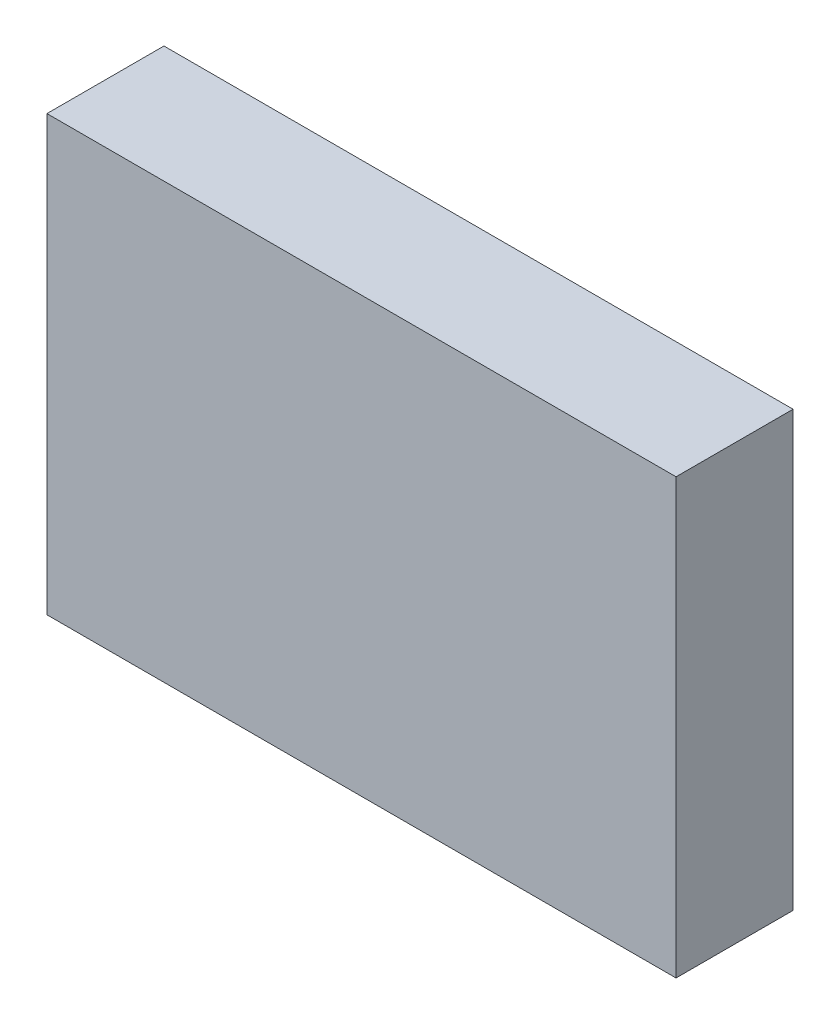
SolidWorks part; units mm, degrees
material "K110"
ref_plane "Front Plane" through (0, 0, 0) normal (0, 0, 1) x (1, 0, 0)
ref_plane "Top Plane" through (0, 0, 0) normal (0, 1, 0) x (1, 0, 0)
ref_plane "Right Plane" through (0, 0, 0) normal (1, 0, 0) x (0, 0, -1)
sketch "Sketch1" plane through (0, 0, 0) normal (0, 1, 0) x (1, 0, 0)
  line L1 (-40, -7.44) -> (40, -7.44)
  line L2 (-40, -7.44) -> (-40, 7.44)
  line L3 (-40, 7.44) -> (40, 7.44)
  line L4 (40, -7.44) -> (40, 7.44)
  line L5 (-40, -7.44) -> (40, 7.44) construction
  line L6 (-40, 7.44) -> (40, -7.44) construction
  point P0 (0, 0)
  dimension "D1" = 80
  dimension "D2" = 14.88
extrude "Boss-Extrude1" add sketch "Sketch1" against normal blind 55.2
